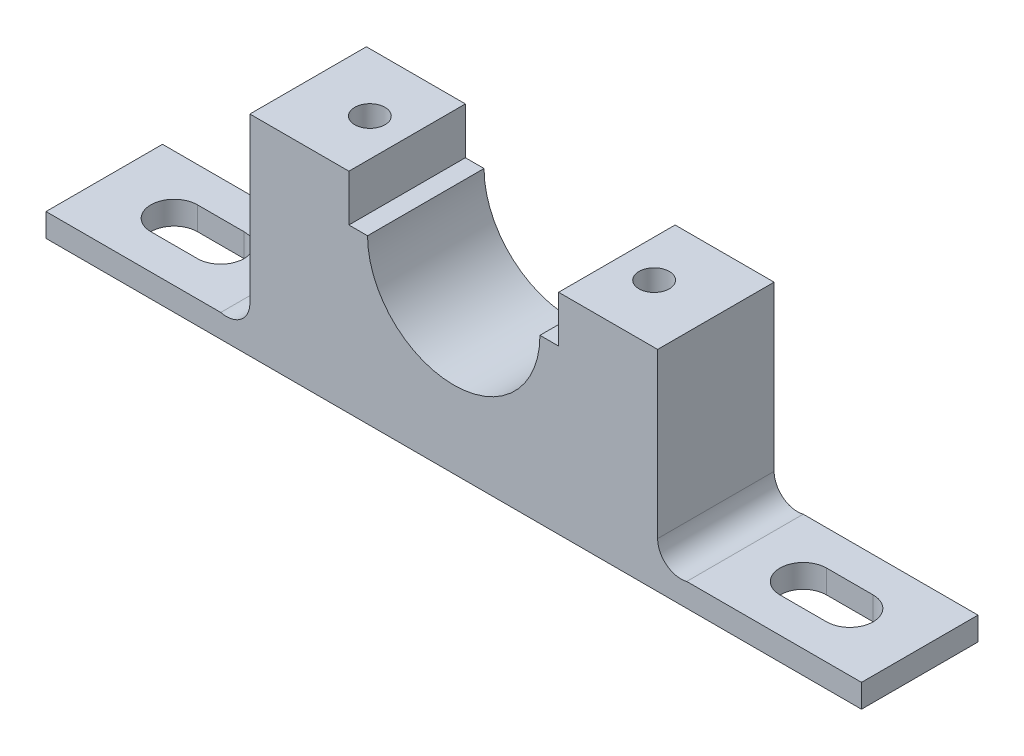
SolidWorks part; units mm, degrees
ref_plane "Front Plane" through (0, 0, 0) normal (0, 0, 1) x (1, 0, 0)
ref_plane "Top Plane" through (0, 0, 0) normal (0, 1, 0) x (1, 0, 0)
ref_plane "Right Plane" through (0, 0, 0) normal (1, 0, 0) x (0, 0, -1)
sketch "Sketch1" plane through (0, 0, 0) normal (0, 0, 1) x (1, 0, 0)
  line L0 (87.5, 0) -> (-87.5, 0)
  line L1 (-87.5, 0) -> (-87.5, 5)
  line L2 (0, 0) -> (0, 45) construction
  line L3 (-87.5, 5) -> (-49.9966, 5)
  line L4 (-22.5, 45) -> (-22.5, 35)
  line L5 (-22.5, 35) -> (-18.5, 35)
  line L6 (-22.5, 45) -> (-43.75, 45)
  line L7 (-43.75, 45) -> (-43.75, 9.8421)
  line L14 (43.75, 45) -> (43.75, 9.8421)
  line L15 (22.5, 45) -> (43.75, 45)
  line L16 (22.5, 35) -> (18.5, 35)
  line L17 (22.5, 45) -> (22.5, 35)
  line L18 (87.5, 5) -> (49.9966, 5)
  line L19 (87.5, 0) -> (87.5, 5)
  arc A0 (-18.5, 35) -> (18.5, 35) centre (0, 35) ccw
  arc A1 (-43.75, 9.8421) -> (-49.9966, 5) centre (-48.75, 9.8421) cw
  arc A4 (43.75, 9.8421) -> (49.9966, 5) centre (48.75, 9.8421) ccw
  point P14 (0, 0)
  point P28 (0, 0)
  dimension "D7" = 18.5
  dimension "D9" = 5
  dimension "D1" = 87.5
  dimension "D2" = 5
  dimension "D3" = 45
  dimension "D4" = 22.5
  dimension "D5" = 10
  dimension "D6" = 4
  dimension "D8" = 21.25
  dimension "D10" = 21.25
sketch "Sketch2" plane through (0, 0, 0) normal (0, 1, 0) x (1, 0, 0)
  line L0 (0, 0) -> (0, 12.5) construction
  line L1 (87.5, 0) -> (-87.5, 0) construction
  line L2 (83.8418, 12.5) -> (-83.8418, 12.5)
  line L3 (0, 0) -> (0, -12.5) construction
  line L4 (83.8418, -12.5) -> (-83.8418, -12.5)
  line L5 (-87.5, 0) -> (-87.5, 9.469)
  line L6 (-87.5, 0) -> (-49.9966, 0) construction
  line L7 (-87.5, 0) -> (-87.5, -9.2851)
  line L8 (-72.5027, 5) -> (-62.5027, 5)
  line L9 (-22.5, 12.5) -> (-22.5, -12.5)
  line L10 (-18.5, -12.5) -> (-18.5, 12.5)
  line L11 (72.5027, -5) -> (62.5027, -5)
  line L12 (18.5, -12.5) -> (18.5, 12.5)
  line L13 (-72.5027, -5) -> (-62.5027, -5)
  line L14 (22.5, 12.5) -> (22.5, -12.5)
  line L15 (72.5027, 5) -> (62.5027, 5)
  line L16 (87.5, 0) -> (87.5, -9.2851)
  line L17 (87.5, 0) -> (87.5, 9.469)
  arc A0 (-83.8418, 12.5) -> (-87.5, 9.469) centre (-83.8418, 8.7769) ccw
  arc A1 (-83.8418, -12.5) -> (-87.5, -9.2851) centre (-83.8418, -8.8113) cw
  circle A2 centre (-30.5, 0) radius 3.25
  arc A3 (-38.0598, 12.5) -> (-38.0598, -12.5) centre (0, 0) ccw
  arc A4 (-43.9434, 12.5) -> (-43.9434, -12.5) centre (-5.8836, 0) ccw
  arc A5 (-72.5027, 5) -> (-72.5027, -5) centre (-72.5027, 0) ccw
  arc A6 (-62.5027, 5) -> (-62.5027, -5) centre (-62.5027, 0) cw
  arc A7 (62.5027, 5) -> (62.5027, -5) centre (62.5027, 0) ccw
  arc A8 (72.5027, 5) -> (72.5027, -5) centre (72.5027, 0) cw
  arc A9 (43.9434, 12.5) -> (43.9434, -12.5) centre (5.8836, 0) cw
  arc A10 (38.0598, 12.5) -> (38.0598, -12.5) centre (0, 0) cw
  circle A11 centre (30.5, 0) radius 3.25
  arc A12 (83.8418, -12.5) -> (87.5, -9.2851) centre (83.8418, -8.8113) ccw
  arc A13 (83.8418, 12.5) -> (87.5, 9.469) centre (83.8418, 8.7769) cw
  point P55 (0, 0)
  dimension "D3" = 57
  dimension "D4" = 6.5
  dimension "D1" = 12.5
  dimension "D2" = 12.5
  dimension "D5" = 10
  dimension "D6" = 10
extrude "Boss-Extrude2" add sketch "Sketch1" along normal blind 12.5 and the other way blind 12.5 contours A0 L16 L17 L15 L14 A4 L18 L19 L0 L1 L3 A1 L7 L6 L4 L5
extrude "Cut-Extrude3" cut sketch "Sketch2" along normal blind 45 contours A11 | A2 | L8 A6 L13 A5 | L15 A7 L11 A8
